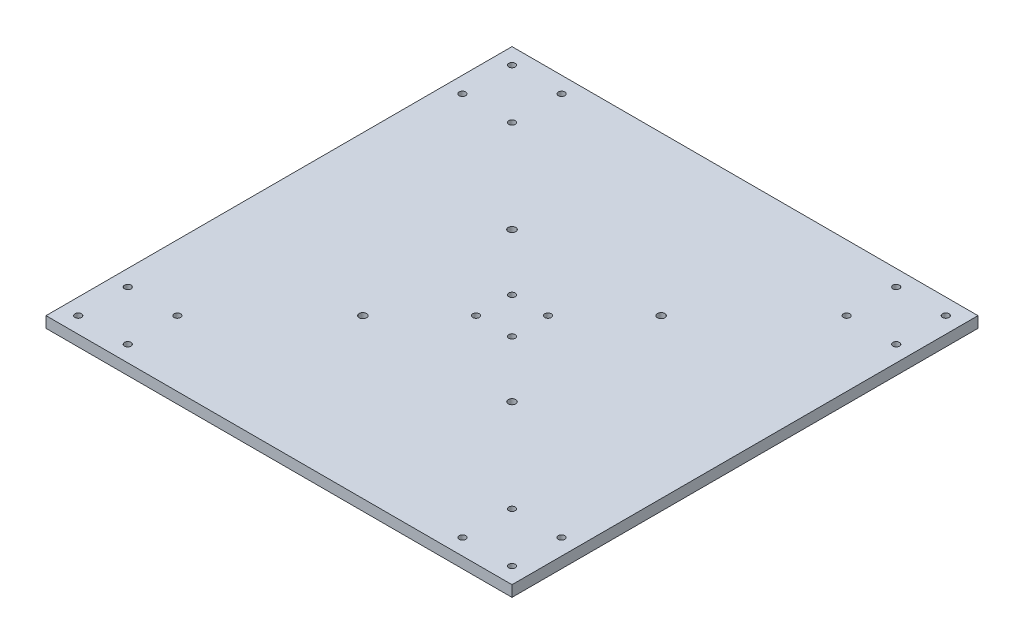
SolidWorks part; units mm, degrees
ref_plane "Front Plane" through (0, 0, 0) normal (0, 0, 1) x (1, 0, 0)
ref_plane "Top Plane" through (0, 0, 0) normal (0, 1, 0) x (1, 0, 0)
ref_plane "Right Plane" through (0, 0, 0) normal (1, 0, 0) x (0, 0, -1)
sketch "Sketch1" plane through (0, 0, 0) normal (0, 1, 0) x (1, 0, 0)
  line L0 (90.9322, -117.8816) -> (117.8816, -117.8816) construction
  line L1 (-126.6319, -126.6319) -> (126.6319, -126.6319)
  line L2 (-126.6319, -126.6319) -> (-126.6319, 126.6319)
  line L3 (-126.6319, 126.6319) -> (126.6319, 126.6319)
  line L4 (126.6319, -126.6319) -> (126.6319, 126.6319)
  line L5 (-126.6319, -126.6319) -> (126.6319, 126.6319) construction
  line L6 (-126.6319, 126.6319) -> (126.6319, -126.6319) construction
  line L7 (-104.4069, 104.4069) -> (104.4069, 104.4069) construction
  line L8 (-104.4069, 104.4069) -> (-104.4069, -104.4069) construction
  line L9 (-104.4069, -104.4069) -> (104.4069, -104.4069) construction
  line L10 (104.4069, 104.4069) -> (104.4069, -104.4069) construction
  line L11 (-104.4069, 104.4069) -> (104.4069, -104.4069) construction
  line L12 (-104.4069, -104.4069) -> (104.4069, 104.4069) construction
  line L13 (-117.8816, -117.8816) -> (-90.9322, -117.8816) construction
  line L14 (-117.8816, -117.8816) -> (-117.8816, -90.9322) construction
  line L15 (-117.8816, -90.9322) -> (-90.9322, -90.9322) construction
  line L16 (-90.9322, -117.8816) -> (-90.9322, -90.9322) construction
  line L17 (-117.8816, -117.8816) -> (-90.9322, -90.9322) construction
  line L18 (-117.8816, -90.9322) -> (-90.9322, -117.8816) construction
  line L19 (90.9322, -117.8816) -> (90.9322, -90.9322) construction
  line L20 (90.9322, -90.9322) -> (117.8816, -90.9322) construction
  line L21 (117.8816, -117.8816) -> (117.8816, -90.9322) construction
  line L22 (90.9322, -117.8816) -> (117.8816, -90.9322) construction
  line L23 (90.9322, -90.9322) -> (117.8816, -117.8816) construction
  line L25 (90.9322, 90.9322) -> (117.8816, 90.9322) construction
  line L26 (90.9322, 90.9322) -> (90.9322, 117.8816) construction
  line L27 (90.9322, 117.8816) -> (117.8816, 117.8816) construction
  line L28 (117.8816, 90.9322) -> (117.8816, 117.8816) construction
  line L29 (90.9322, 90.9322) -> (117.8816, 117.8816) construction
  line L30 (90.9322, 117.8816) -> (117.8816, 90.9322) construction
  line L31 (-117.8816, 90.9322) -> (-90.9322, 90.9322) construction
  line L32 (-117.8816, 90.9322) -> (-117.8816, 117.8816) construction
  line L33 (-117.8816, 117.8816) -> (-90.9322, 117.8816) construction
  line L34 (-90.9322, 90.9322) -> (-90.9322, 117.8816) construction
  line L35 (-117.8816, 90.9322) -> (-90.9322, 117.8816) construction
  line L36 (-117.8816, 117.8816) -> (-90.9322, 90.9322) construction
  line L38 (-9.779, 9.779) -> (9.779, 9.779) construction
  line L39 (-9.779, 9.779) -> (-9.779, -9.779) construction
  line L40 (-9.779, -9.779) -> (9.779, -9.779) construction
  line L41 (-42.8642, -42.8642) -> (42.8642, 42.8642) construction
  line L42 (-42.8642, 42.8642) -> (42.8642, -42.8642) construction
  line L43 (-40.513, -40.513) -> (40.513, -40.513) construction
  line L44 (-40.513, -40.513) -> (-40.513, 40.513) construction
  line L45 (-40.513, 40.513) -> (40.513, 40.513) construction
  line L46 (40.513, -40.513) -> (40.513, 40.513) construction
  line L47 (-40.513, -40.513) -> (40.513, 40.513) construction
  line L48 (-40.513, 40.513) -> (40.513, -40.513) construction
  line L49 (9.779, 9.779) -> (9.779, -9.779) construction
  line L50 (-9.779, 9.779) -> (9.779, -9.779) construction
  line L51 (-9.779, -9.779) -> (9.779, 9.779) construction
  circle A0 centre (-117.8816, -117.8816) radius 1.778
  circle A1 centre (-90.9322, -117.8816) radius 1.778
  circle A2 centre (-117.8816, -90.9322) radius 1.778
  circle A3 centre (-90.9322, -90.9322) radius 1.778
  circle A4 centre (90.9322, -117.8816) radius 1.778
  circle A5 centre (117.8816, -117.8816) radius 1.778
  circle A6 centre (90.9322, -90.9322) radius 1.778
  circle A7 centre (117.8816, -90.9322) radius 1.778
  circle A8 centre (90.9322, 90.9322) radius 1.778
  circle A9 centre (117.8816, 90.9322) radius 1.778
  circle A10 centre (90.9322, 117.8816) radius 1.778
  circle A11 centre (117.8816, 117.8816) radius 1.778
  circle A12 centre (-117.8816, 90.9322) radius 1.778
  circle A13 centre (-90.9322, 90.9322) radius 1.778
  circle A14 centre (-117.8816, 117.8816) radius 1.778
  circle A15 centre (-90.9322, 117.8816) radius 1.778
  circle A16 centre (-9.779, -9.779) radius 1.778
  circle A17 centre (-40.513, 40.513) radius 2.032
  circle A18 centre (40.513, 40.513) radius 2.032
  circle A19 centre (-40.513, -40.513) radius 2.032
  circle A20 centre (40.513, -40.513) radius 2.032
  circle A21 centre (9.779, -9.779) radius 1.778
  circle A22 centre (-9.779, 9.779) radius 1.778
  circle A23 centre (9.779, 9.779) radius 1.778
  point P0 (0, 0)
  point P6 (0, 0)
  point P11 (0, 0)
  point P50 (0, 0)
  dimension "D1" = 22.225
extrude "Boss-Extrude1" add sketch "Sketch1" along normal blind 5.9944
